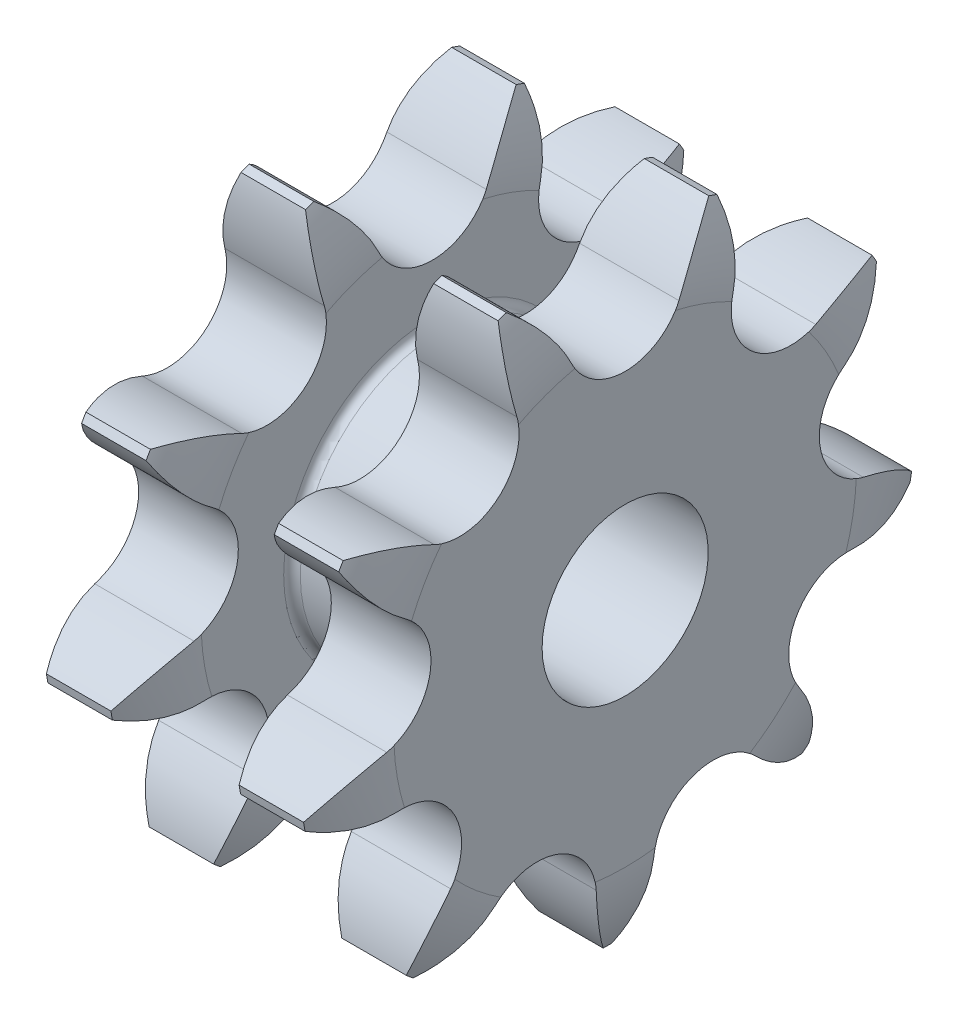
SolidWorks part; units mm, degrees
ref_plane "Plane1" through (0, 0, 0) normal (0, 0, 1) x (1, 0, 0)
ref_plane "Plane2" through (0, 0, 0) normal (0, 1, 0) x (1, 0, 0)
ref_plane "Plane3" through (0, 0, 0) normal (1, 0, 0) x (0, 0, -1)
sketch "Clipboard" plane through (0, 0, 0) normal (0, 1, 0) x (1, 0, 0)
  line L0 (0, 0) -> (12.5436, -1.9867)
  line L1 (-15, 0) -> (100, 0) construction
  line L2 (0, 0) -> (-0.8416, 0.9512)
  line L3 (0, 0) -> (-11.863, 4.5341)
  line L4 (0, 0) -> (3.0618, 0.4849)
  line L5 (0, 0) -> (-2.8109, -1.0484)
  line L6 (0, 0) -> (-17.5077, -11.8125)
  line L7 (-0.8416, 0.9512) -> (22.0505, 5.4009)
  line L8 (-76.2, 38.1) -> (-75.2, 38.1)
  line L9 (-73.4259, 41.6592) -> (-72.8306, 41.7344)
  line L10 (-73.4741, 12.7512) -> (-59.5541, 12.7512)
  circle A0 centre (0, 0) radius 4.255
  circle A1 centre (0, 0) radius 10.1515
  circle A2 centre (0, 0) radius 25
  dimension "Num_teeth" = 9
  dimension "Thickness" = 21.12
  dimension "Fillet_rad" = 0.6
sketch "BasProSke" plane through (0, 0, 0) normal (0, 1, 0) x (1, 0, 0)
  line L0 (-10, 0) -> (60, 0) construction
  line L1 (0, 0) -> (0, 16.7129)
  line L2 (0, 0) -> (21.12, 0)
  line L3 (21.12, 0) -> (21.12, 16.7129)
  line L4 (19.85, 22.2487) -> (1.27, 22.2487)
  arc A0 (0, 16.7129) -> (1.27, 22.2487) centre (12.7, 16.7129) cw
  arc A1 (21.12, 16.7129) -> (19.85, 22.2487) centre (8.42, 16.7129) ccw
  dimension "D1" = 12.7
  dimension "Thickness" = 21.12
  dimension "Diameter" = 44.4973
  dimension "G1" = 1.27
revolve "Base-Revolve" add sketch "BasProSke" angle 360 about L0
sketch "GrvSke" plane through (0, 0, 0) normal (0, 1, 0) x (1, 0, 0)
  line L0 (7.2, 16.7129) -> (7.2, 10.7515)
  line L1 (7.8, 10.1515) -> (13.32, 10.1515)
  line L2 (13.92, 10.7515) -> (13.92, 16.7129)
  line L3 (5.93, 22.2487) -> (15.19, 22.2487)
  line L4 (10.56, 0) -> (10.56, 52.07) construction
  line L5 (-10, 0) -> (60, 0) construction
  line L6 (0, 0) -> (35.56, 0) construction
  arc A0 (13.92, 16.7129) -> (15.19, 22.2487) centre (26.62, 16.7129) cw
  arc A1 (7.2, 16.7129) -> (5.93, 22.2487) centre (-5.5, 16.7129) ccw
  arc A2 (7.2, 10.7515) -> (7.8, 10.1515) centre (7.8, 10.7515) ccw
  arc A3 (13.32, 10.1515) -> (13.92, 10.7515) centre (13.32, 10.7515) ccw
  dimension "D1" = 12.7
  dimension "Diameter" = 44.4973
  dimension "Fillet_rad" = 0.6
  dimension "G1" = 1.27
  dimension "Grv_width" = 6.72
revolve "Groove" cut sketch "GrvSke" angle 360 about L6
sketch "TooCutSke" plane through (0, 0, 0) normal (1, 0, 0) x (0, 0, -1)
  line L0 (0, 18.6087) -> (3.8949, 16.7925) construction
  line L1 (0, 0) -> (0, 107) construction
  line L2 (0, 18.6087) -> (-10, 18.6087) construction
  line L3 (0, 18.6087) -> (-3.8949, 16.7925) construction
  arc A0 (3.8949, 16.7925) -> (7.8075, 21.3669) centre (14.0756, 12.0451) cw
  arc A1 (3.8949, 16.7925) -> (-3.8949, 16.7925) centre (0, 18.6087) cw
  arc A2 (-3.8949, 16.7925) -> (-7.8075, 21.3669) centre (-14.0756, 12.0451) ccw
  arc A3 (7.8075, 21.3669) -> (-7.8075, 21.3669) centre (0, 0) ccw
extrude "ToothCut" cut sketch "TooCutSke" along normal through all
pattern_circular "TeethCuts" count 9 every 40 about axis through (-10, 0, 0) along (1, 0, 0) of "ToothCut"
sketch "HubNeaOneSke" plane through (0, 0, 0) normal (-1, 0, 0) x (0, 0, 1)
  circle A0 centre (0, 0) radius 10.1515
  dimension "Diameter" = 20.303
extrude "HubNearOne" [suppressed] add sketch "HubNeaOneSke" along normal blind 2.2005
fillet "HubNearOneFillet" [suppressed] radius 0.6
sketch "HubNeaBotSke" plane through (0, 0, 0) normal (-1, 0, 0) x (0, 0, 1)
  circle A0 centre (0, 0) radius 10.1515
  dimension "Diameter" = 20.303
extrude "HubNearBoth" [suppressed] add sketch "HubNeaBotSke" along normal blind 1.1003
fillet "HubNearBothFillet" [suppressed] radius 0.6
ref_plane "FarPln" through (21.12, 0, 0) normal (1, 0, 0) x (0, 0, -1)
sketch "HubFarSke" plane through (21.12, 0, 0) normal (1, 0, 0) x (0, 0, -1)
  circle A0 centre (0, 0) radius 10.1515
  dimension "Diameter" = 20.303
extrude "HubFar" [suppressed] add sketch "HubFarSke" along normal blind 1.1003
fillet "HubFarFillet" [suppressed] radius 0.6
sketch "BorSke" plane through (0, 0, 0) normal (1, 0, 0) x (0, 0, -1)
  circle A0 centre (0, 0) radius 6
  dimension "Diameter" = 12
extrude "Bore" cut sketch "BorSke" along normal mid plane 46.641
sketch "KeySke" plane through (0, 0, 0) normal (1, 0, 0) x (0, 0, -1)
  line L0 (-1, 0) -> (-1, 7)
  line L1 (-1, 7) -> (1, 7)
  line L2 (1, 7) -> (1, 0)
  line L3 (0, 0) -> (0, 34) construction
  line L4 (-1, 0) -> (1, 0)
  dimension "Offset" = 7
  dimension "Width" = 2
extrude "Keyway" [suppressed] cut sketch "KeySke" along normal mid plane 46.641
pattern_circular "Keyway2" [suppressed] count 2 every 90 about axis through (-10, 0, 0) along (1, 0, 0)
equation "' \"Pitch@Clipboard\" = 12.7"
equation "' \"Num_strands@Clipboard\" = 2"
equation "' \"Num_teeth@Clipboard\" = 9"
equation "' \"Hub_dia@Clipboard\" = 50"
equation "' \"Overall_len@Clipboard\" = 3"
equation "' \"Diameter@BorSke\" = 12"
equation "' \"T_dim@Clipboard\" = 1"
equation "' \"Width@KeySke\" = 2"
equation "' \"Dr@Clipboard\" = 8.51"
equation "' \"Face_width@Clipboard\" = 7.2"
equation "' \"Side_radius@Clipboard\" = 12.7"
equation "' \"Side_relief@Clipboard\" = 1.27"
equation "' \"Transv_pitch@Clipboard\" = 13.92"
equation "' \"Show_teeth@Clipboard\" = 9"
equation "' \"Fillet_rad@Clipboard\" = 0.6"
equation "' \"Plate_wid@Clipboard\" = 11.8"
equation "\"Num_teeth@Clipboard\" = int( \"Num_teeth@Clipboard\" )"
equation "\"Num_teeth@Clipboard\" = ((sgn( \"Num_teeth@Clipboard\" - 5.0)+1)*( \"Num_teeth@Clipboard\" - 5.0))/2 +5.0"
equation "\"Num_teeth@Clipboard\" = ((sgn( \"Num_teeth@Clipboard\" - 200.0)-1)*( \"Num_teeth@Clipboard\" - 200.0))/-2 +200.0"
equation "\"MHD@Clipboard\" = \"Pitch@Clipboard\" * (1.0 / tan(3.14159265 / \"Num_teeth@Clipboard\" )) - 1.05 * \"Plate_wid@Clipboard\" - 2.0 * \"Fillet_rad@Clipboard\" - 1.0"
equation "\"Thickness@Clipboard\"  = \"Face_width@Clipboard\" + (\"Num_strands@Clipboard\" - 1) * \"Transv_pitch@Clipboard\""
equation "\"OAL@Clipboard\" = \"Thickness@Clipboard\" + 2 * \"Fillet_rad@Clipboard\" + 1"
equation "\"MHD@Clipboard\" = ((sgn( \"MHD@Clipboard\" - \"Hub_dia@Clipboard\" )-1)*( \"MHD@Clipboard\" - \"Hub_dia@Clipboard\" ))/-2+ \"Hub_dia@Clipboard\""
equation "\"OAL@Clipboard\" = ((sgn( \"OAL@Clipboard\" - \"Overall_len@Clipboard\" )+1)*( \"OAL@Clipboard\" - \"Overall_len@Clipboard\" ))/2 + \"Overall_len@Clipboard\" + 0.0005"
equation "\"Num_teeth@TeethCuts\" = int( \"Show_teeth@Clipboard\" ) + 1"
equation "\"Num_teeth@TeethCuts\" = ((sgn( \"Num_teeth@TeethCuts\" - \"Num_teeth@Clipboard\" )-1)*( \"Num_teeth@TeethCuts\" - \"Num_teeth@Clipboard\" ))/-2+ \"Num_teeth@Clipboard\""
equation "\"Num_teeth@TeethCuts\" = ((sgn( \"Num_teeth@TeethCuts\" - 2.0)+1)*( \"Num_teeth@TeethCuts\" - 2.0))/2 +2.0"
equation "\"Angle@TeethCuts\" = 360.0 / \"Num_teeth@Clipboard\""
equation "\"Seat_radius@TooCutSke\" = ( \"Pitch@Clipboard\" / 2.0) / sin(3.14159265 / \"Num_teeth@Clipboard\" ) - \"Dr@Clipboard\" / 2.0 + \"Dr@Clipboard\" * 0.505"
equation "\"R1@TooCutSke\"  = \"Dr@Clipboard\" * 0.505"
equation "\"X@TooCutSke\" = 140.0 - (90.0 / \"Num_teeth@Clipboard\")"
equation "\"R2@TooCutSke\" = 0.12 * \"Dr@Clipboard\" * ( \"Num_teeth@Clipboard\" + 2.0)"
equation "\"Overcut@TooCutSke\" = 0.5 + 0.625 * \"Pitch@Clipboard\" - 0.5 * \"Dr@Clipboard\"  +  \"Pitch@Clipboard\" / 2.0 / sin(3.14159265 / \"Num_teeth@Clipboard\" )"
equation "\"Diameter@BasProSke\" = 2.0 * ( 0.625 * \"Pitch@Clipboard\" - 0.5 * \"Dr@Clipboard\"  +  \"Pitch@Clipboard\" / 2.0 / sin(3.14159265 / \"Num_teeth@Clipboard\" ))"
equation "\"Thickness@BasProSke\"  = \"Thickness@Clipboard\""
equation "\"G1@BasProSke\" =  \"Side_relief@Clipboard\""
equation "\"G2@BasProSke\" =  \"Side_relief@Clipboard\""
equation "\"D1@BasProSke\" =  \"Side_radius@Clipboard\""
equation "\"Diameter@GrvSke\" = \"Diameter@BasProSke\""
equation "\"G1@GrvSke\" = \"Side_relief@Clipboard\""
equation "\"D1@GrvSke\" = \"Side_radius@Clipboard\""
equation "\"Grv_diam@GrvSke\" =  \"Pitch@Clipboard\" * (1.0 / tan(3.14159265 / \"Num_teeth@Clipboard\" ))- 1.05 * \"Plate_wid@Clipboard\" - 2.0 * \"Fillet_rad@Clipboard\" - 1.0"
equation "\"Grv_width@GrvSke\" =  \"Transv_pitch@Clipboard\" - \"Face_width@Clipboard\""
equation "\"Offset@GrvSke\" = \"Grv_width@GrvSke\" / 2.0 + \"Face_width@Clipboard\""
equation "\"Fillet_rad@GrvSke\" = \"Fillet_rad@Clipboard\""
equation "\"Diameter@HubNeaOneSke\" = \"MHD@Clipboard\""
equation "\"Length@HubNearOne\" = \"OAL@Clipboard\" - \"Thickness@BasProSke\""
equation "\"Diameter@HubNeaBotSke\" = \"MHD@Clipboard\""
equation "\"Length@HubNearBoth\" = ( \"OAL@Clipboard\" - \"Thickness@BasProSke\" ) / 2.0"
equation "\"D1@HubNearOneFillet\" = \"Fillet_rad@Clipboard\""
equation "\"D1@HubNearBothFillet\" = \"Fillet_rad@Clipboard\""
equation "\"Thickness@FarPln\" = \"Thickness@BasProSke\""
equation "\"Diameter@HubFarSke\" = \"MHD@Clipboard\""
equation "\"Length@HubFar\" = ( \"OAL@Clipboard\" - \"Thickness@BasProSke\" ) / 2.0"
equation "\"D1@HubFarFillet\" = \"Fillet_rad@Clipboard\""
equation "\"D1@Bore\" = \"OAL@Clipboard\" * 2.0"
equation "\"D1@Keyway\" = \"OAL@Clipboard\" * 2.0"
equation "\"Offset@KeySke\" = \"T_dim@Clipboard\" + \"Diameter@BorSke\" / 2.0"
